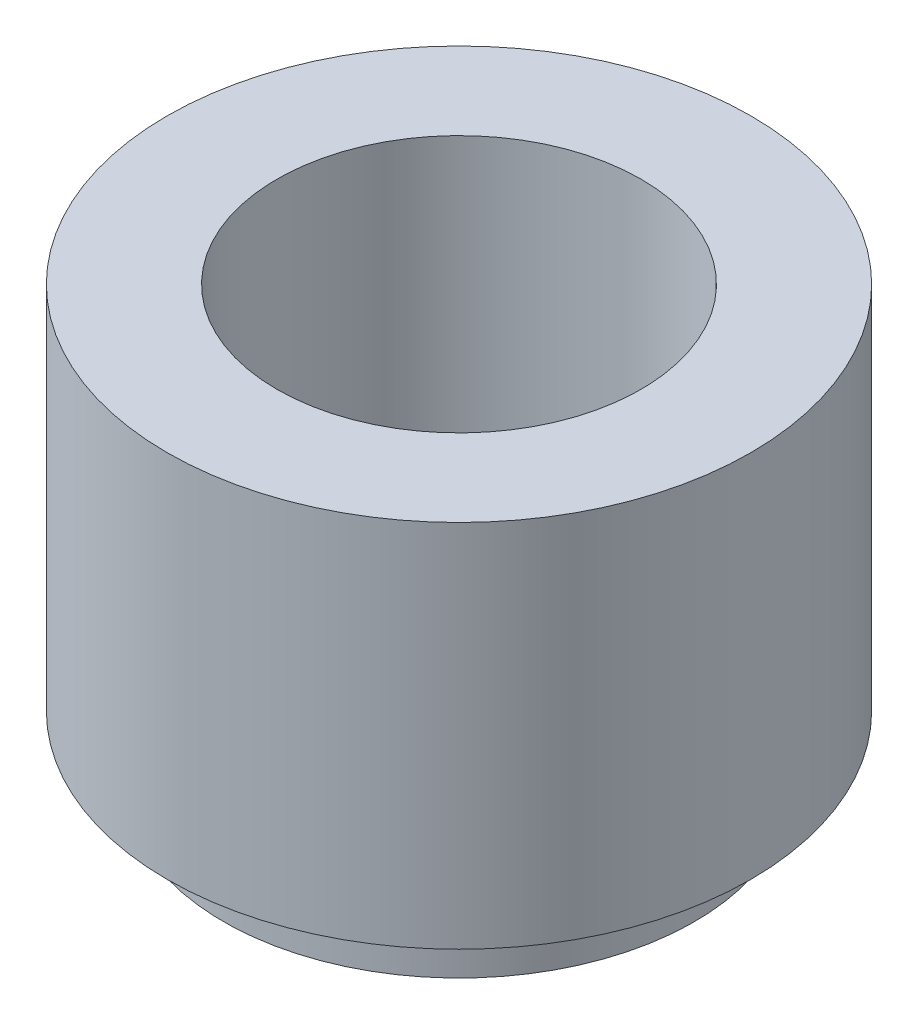
SolidWorks part; units mm, degrees
material "AISI 304"
ref_plane "Front Plane" through (0, 0, 0) normal (0, 0, 1) x (1, 0, 0)
ref_plane "Top Plane" through (0, 0, 0) normal (0, 1, 0) x (1, 0, 0)
ref_plane "Right Plane" through (0, 0, 0) normal (1, 0, 0) x (0, 0, -1)
sketch "Sketch1" plane through (0, 0, 0) normal (0, 1, 0) x (1, 0, 0)
  circle A0 centre (0, 0) radius 9.525
  dimension "D1" = 19.05
extrude "Boss-Extrude1" add sketch "Sketch1" along normal blind 5.715
sketch "Sketch2" plane through (0, 0, 0) normal (0, -1, 0) x (1, 0, 0)
  line L1 (0, -10.9985) -> (9.525, -5.4993)
  line L2 (9.525, -5.4993) -> (9.525, 5.4993)
  line L3 (9.525, 5.4993) -> (0, 10.9985)
  line L4 (0, 10.9985) -> (-9.525, 5.4993)
  line L5 (-9.525, 5.4993) -> (-9.525, -5.4993)
  line L6 (-9.525, -5.4993) -> (0, -10.9985)
  circle A0 centre (0, 0) radius 9.525 construction
  circle A2 centre (0, 0) radius 9.525 construction
extrude "Boss-Extrude2" add sketch "Sketch2" along normal blind 6.35
sketch "Sketch3" plane through (0, -6.35, 0) normal (0, -1, 0) x (1, 0, 0)
  circle A0 centre (0, 0) radius 7.9375
  dimension "D1" = 15.875
extrude "Boss-Extrude3" add sketch "Sketch3" along normal blind 1.0583
sketch "Sketch4" plane through (0, -7.4083, 0) normal (0, -1, 0) x (1, 0, 0)
  circle A0 centre (0, 0) radius 7.6835
  circle A1 centre (0, 0) radius 7.9375 construction
  dimension "D1" = 0.254
extrude "Boss-Extrude4" add sketch "Sketch4" along normal blind 1.0583
hole_wizard "1/4-18 NPSM Tapped Hole2" positions "Sketch9" profile "Sketch10" tap size "1/4-18 NPSM" standard "ANSI Inch" end condition through all
sketch "Sketch9" plane through (0, 5.715, 0) normal (0, 1, 0) x (1, 0, 0)
  point P0 (0, 0)
sketch "Sketch10" plane through (0, 5.715, 0) normal (1, 0, 0) x (0, 0, 1)
  line L0 (0, 0) -> (0, 14.1817)
  line L1 (0, 14.1817) -> (5.9436, 14.1817)
  line L2 (5.9436, 14.1817) -> (5.9436, 0)
  line L5 (5.9436, 0) -> (0, 0)
  line L11 (0, -6.35) -> (0, 107.95) construction
  dimension "Thru Tap Drill Dia." = 11.8872
  dimension "Thru Tap Drill Depth" = 14.1817
cosmetic thread "Hole Thread1" parameters "D2"=13.3604
sketch "Sketch11" plane through (0, 5.715, 0) normal (0, 1, 0) x (1, 0, 0)
  circle A0 centre (0, 0) radius 10.9985
  circle A1 centre (0, 0) radius 9.525
  circle A2 centre (0, 0) radius 9.525 construction
extrude "Cut-Extrude1" cut sketch "Sketch11" against normal through all
